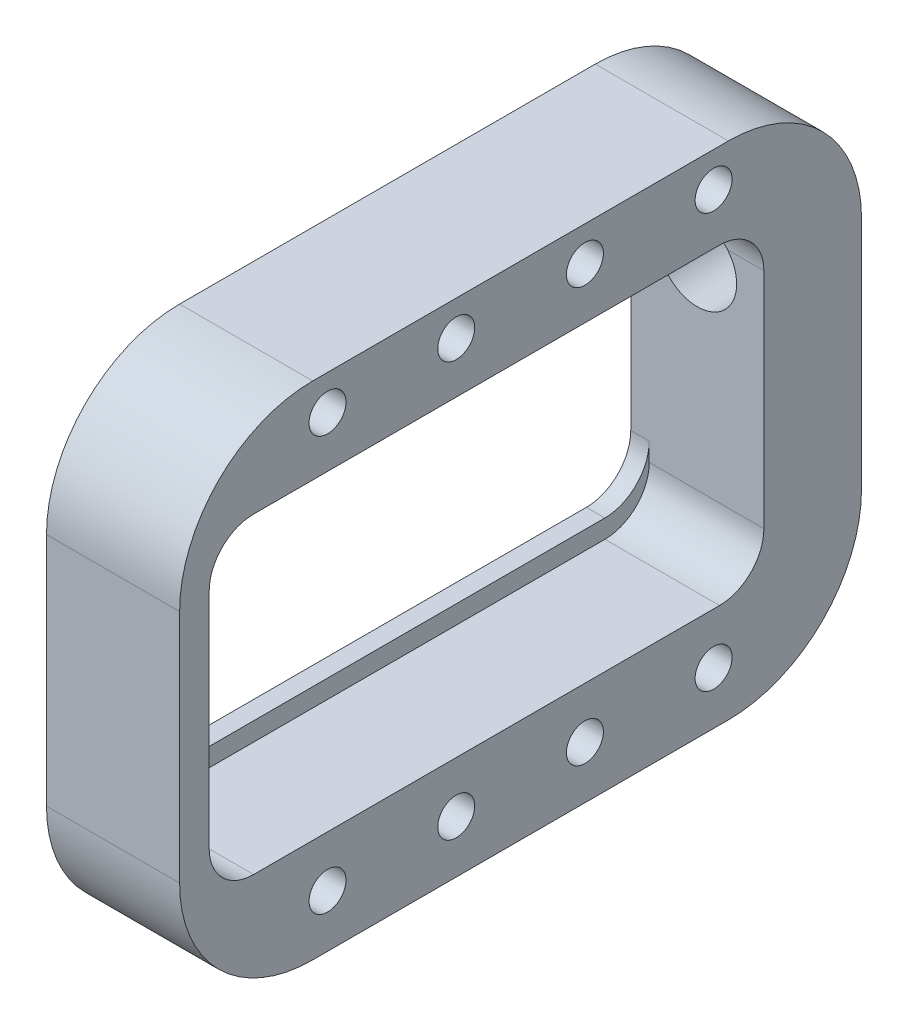
SolidWorks part; units mm, degrees
material "6061-T6 (SS)"
ref_plane "Front Plane" through (0, 0, 0) normal (0, 0, 1) x (1, 0, 0)
ref_plane "Top Plane" through (0, 0, 0) normal (0, 1, 0) x (1, 0, 0)
ref_plane "Right Plane" through (0, 0, 0) normal (1, 0, 0) x (0, 0, -1)
sketch "Sketch1" plane through (0, 0, 0) normal (1, 0, 0) x (0, 0, -1)
  line L0 (0, 22.2885) -> (0, -22.2885) construction
  line L1 (-26.3525, 22.2885) -> (32.1945, 22.2885)
  line L2 (-26.3525, 22.2885) -> (-26.3525, -22.2885)
  line L3 (-26.3525, -22.2885) -> (32.1945, -22.2885)
  line L4 (32.1945, 22.2885) -> (32.1945, -22.2885)
  line L5 (-23.8125, 13.3985) -> (23.8125, 13.3985)
  line L6 (-23.8125, 13.3985) -> (-23.8125, -13.3985)
  line L7 (-23.8125, -13.3985) -> (23.8125, -13.3985)
  line L8 (23.8125, 13.3985) -> (23.8125, -13.3985)
  line L9 (23.8125, -13.3985) -> (-23.8125, 13.3985) construction
  dimension "D1" = 8.89
  dimension "D2" = 2.54
  dimension "D3" = 47.625
  dimension "D4" = 26.797
  dimension "D5" = 8.382
  dimension "D6" = 8.89
extrude "Boss-Extrude1" add sketch "Sketch1" along normal mid plane 11.43
sketch "Sketch9" plane through (0, 0, -23.8125) normal (0, 0, 1) x (1, 0, 0)
  line L0 (-5.715, 13.3985) -> (-5.715, 11.811)
  line L1 (-5.715, -13.3985) -> (-4.1275, -13.3985)
  line L2 (-5.715, -13.3985) -> (-5.715, -11.811)
  line L3 (-5.715, -11.811) -> (-4.1275, -11.811)
  line L4 (-4.1275, -13.3985) -> (-4.1275, -11.811)
  line L5 (-5.715, 13.3985) -> (-4.1275, 13.3985)
  line L6 (-5.715, 11.811) -> (-4.1275, 11.811)
  line L7 (-4.1275, 13.3985) -> (-4.1275, 11.811)
  line L9 (-5.715, -13.3985) -> (-5.715, 13.3985) construction
  dimension "D1" = 23.622
  dimension "D2" = 1.5875
extrude "Boss-Extrude2" add sketch "Sketch9" along normal up to next
fillet "Fillet11" radius 3.81 4 edges at (-4.9213, -11.811, -23.8125) (-4.9212, 11.811, -23.8125) (-4.9213, -11.811, 23.8125) (-4.9212, 11.811, 23.8125)
fillet "Fillet12" radius 3.81 4 edges at (0.7937, 13.3985, 23.8125) (0.7937, -13.3985, 23.8125) (0.7938, -13.3985, -23.8125) (0.7937, 13.3985, -23.8125)
sketch "Sketch21" plane through (5.715, 0, 0) normal (1, 0, 0) x (0, 0, -1)
  line L0 (32.1945, -22.2885) -> (32.1945, 22.2885) construction
  line L1 (-26.3525, -22.2885) -> (32.1945, -22.2885) construction
  circle A0 centre (33.4645, -9.5885) radius 2.54
  dimension "D1" = 5.08
  dimension "D2" = 1.27
  dimension "D3" = 12.7
hole_wizard "1/4 Clearance Hole1" positions "Sketch5" profile "Sketch4" hole size "1/4" standard "ANSI Inch"
sketch "Sketch5" plane through (-2.5308, 6.493, -32.1945) normal (0, 0, 1) x (1, 0, 0)
  line L12 (8.2458, 15.7955) -> (8.2458, -28.7815) construction
  line L16 (-3.1842, -19.8915) -> (8.2458, -19.8915) construction
  line L17 (-3.1842, 15.7955) -> (-3.1842, -28.7815) construction
  line L26 (-3.1842, 6.9055) -> (8.2458, 6.9055) construction
  line L28 (2.5308, 6.9055) -> (2.5308, 0.9365) construction
  line L30 (2.5308, -19.8915) -> (2.5308, -13.9225) construction
  line L31 (2.5308, 0.9365) -> (2.5308, -13.9225) construction
  line L32 (8.2458, -28.7815) -> (8.2458, 15.7955) construction
  point P95 (2.5308, 0.9365)
  dimension "D1" = 5.969
sketch "Sketch4" plane through (0, 7.4295, -32.1945) normal (1, 0, 0) x (0, 1, 0)
  line L0 (0, 0) -> (0, 10.9198)
  line L1 (0, 10.9198) -> (3.3782, 8.89)
  line L2 (3.3782, 8.89) -> (3.3782, 0)
  line L5 (3.3782, 0) -> (0, 0)
  line L10 (0, 10.9198) -> (-3.3782, 8.89) construction
  line L11 (0, -6.35) -> (0, 107.95) construction
  dimension "Hole Dia." = 6.7564
  dimension "Hole Depth" = 8.89
  dimension "Drill Angle" = 118
sketch "Sketch14" plane through (-5.715, 0, 0) normal (-1, 0, 0) x (0, 0, 1)
  line L0 (-32.1945, -17.78) -> (-19.4945, -17.78) construction
  line L1 (-32.1945, 17.78) -> (-19.4945, 17.78) construction
  line L2 (-19.4945, 17.78) -> (-8.4455, 17.78) construction
  line L3 (13.6525, 17.78) -> (26.3525, 17.78) construction
  line L4 (-19.4945, -17.78) -> (-8.4455, -17.78) construction
  line L5 (13.6525, -17.78) -> (26.3525, -17.78) construction
  line L6 (-19.1091, 17.78) -> (-19.1091, 22.2885) construction
  line L7 (-7.0267, -17.78) -> (-7.0267, -22.2885) construction
  line L8 (-8.4455, -17.78) -> (2.6035, -17.78) construction
  line L9 (2.6035, -17.78) -> (13.6525, -17.78) construction
  line L10 (2.6035, 17.78) -> (13.6525, 17.78) construction
  line L11 (-8.4455, 17.78) -> (2.6035, 17.78) construction
  line L12 (26.3525, -22.2885) -> (-32.1945, -22.2885) construction
  line L13 (-32.1945, 22.2885) -> (26.3525, 22.2885) construction
  line L14 (26.3525, 22.2885) -> (26.3525, -22.2885) construction
  line L15 (-32.1945, -22.2885) -> (-32.1945, 22.2885) construction
  point P0 (-19.4945, 17.78)
  point P1 (-19.4945, -17.78)
  point P2 (13.6525, -17.78)
  point P3 (13.6525, 17.78)
  dimension "D1" = 12.7
  dimension "D2" = 35.56
hole_wizard "#6-32 Tapped Hole1" positions "Sketch16" profile "Sketch15" tap size "#6-32" standard "ANSI Inch" end condition through all
sketch "Sketch16" plane through (5.715, 17.9556, 19.2123) normal (-1, 0, 0) x (0, 0, 1)
  point P0 (-27.6578, -0.1756)
  point P3 (-16.6088, -0.1756)
  point P6 (-5.5598, -0.1756)
  point P9 (-38.7068, -0.1756)
  point P12 (-38.7068, -35.7356)
  point P15 (-27.6578, -35.7356)
  point P18 (-16.6088, -35.7356)
  point P21 (-5.5598, -35.7356)
cosmetic thread "Hole Thread1" parameters "D2"=3.5052
cosmetic thread "Hole Thread2" parameters "D2"=3.5052
cosmetic thread "Hole Thread3" parameters "D2"=3.5052
cosmetic thread "Hole Thread4" parameters "D2"=3.5052
cosmetic thread "Hole Thread5" parameters "D2"=3.5052
cosmetic thread "Hole Thread6" parameters "D2"=3.5052
cosmetic thread "Hole Thread7" parameters "D2"=3.5052
cosmetic thread "Hole Thread8" parameters "D2"=3.5052
sketch "Sketch15" plane through (5.715, 17.78, -8.4455) normal (0, 1, 0) x (0, 0, -1)
  line L0 (0, 0) -> (0, 11.43)
  line L1 (0, 11.43) -> (1.3525, 11.43)
  line L2 (1.3525, 11.43) -> (1.3525, 0)
  line L5 (1.3525, 0) -> (0, 0)
  line L11 (0, -6.35) -> (0, 107.95) construction
  dimension "Thru Tap Drill Dia." = 2.7051
  dimension "Thru Tap Drill Depth" = 11.43
sketch "Sketch22" plane through (-5.715, 0, 0) normal (-1, 0, 0) x (0, 0, 1)
  line L0 (-32.1945, 22.2885) -> (26.3525, 22.2885) construction
  line L1 (-32.1945, 29.9417) -> (26.3525, 29.9417)
  line L2 (-32.1945, 29.9417) -> (-32.1945, 20.7645)
  line L3 (-32.1945, 20.7645) -> (26.3525, 20.7645)
  line L4 (26.3525, 29.9417) -> (26.3525, 20.7645)
  line L5 (-32.1945, 29.9417) -> (26.3525, 20.7645) construction
  line L6 (-32.1945, 20.7645) -> (26.3525, 29.9417) construction
  line L7 (-32.1945, -22.2885) -> (-32.1945, 22.2885) construction
  line L8 (26.3525, 22.2885) -> (26.3525, -22.2885) construction
  point P4 (-2.921, 25.3531)
  dimension "D1" = 1.524
extrude "Cut-Extrude4" cut sketch "Sketch22" against normal through all
fillet "Fillet14" radius 11.43 2 edges at (0, -22.2885, 26.3525) (0, 20.7645, 26.3525)
fillet "Fillet13" radius 11.43 2 edges at (0, -22.2885, -32.1945) (0, 20.7645, -32.1945)
sketch "Sketch11" plane through (5.715, 0, 0) normal (1, 0, 0) x (0, 0, -1)
  line L0 (32.1945, -10.8585) -> (32.1945, 9.3345) construction
  line L1 (32.1945, 14.6923) -> (30.861, 14.6923)
  line L2 (32.1945, 14.6923) -> (32.1945, -16.2163)
  line L3 (32.1945, -16.2163) -> (30.861, -16.2163)
  line L4 (30.861, 14.6923) -> (30.861, -16.2163)
  arc A0 (20.7645, -22.2885) -> (32.1945, -10.8585) centre (20.7645, -10.8585) ccw construction
  arc A2 (32.1945, 9.3345) -> (20.7645, 20.7645) centre (20.7645, 9.3345) ccw construction
  dimension "D1" = 30.861
extrude "Cut-Extrude2" [suppressed] cut sketch "Sketch11" against normal blind 1.016
ref_point "Point1" [suppressed]
sketch "Sketch17" plane through (-5.715, 0, 0) normal (-1, 0, 0) x (0, 0, 1)
  line L0 (-44.2595, 37.338) -> (-44.2595, -38.862)
  line L1 (-44.2595, 37.338) -> (116.0145, 37.338)
  line L2 (-44.2595, -38.862) -> (116.0145, -38.862)
  line L3 (116.0145, 37.338) -> (116.0145, -38.862)
  line L4 (45.4025, 20.7645) -> (45.4025, -22.2885) construction
  line L5 (45.4025, 20.7645) -> (103.9495, 20.7645) construction
  line L6 (45.4025, -22.2885) -> (103.9495, -22.2885) construction
  line L7 (103.9495, 20.7645) -> (103.9495, -22.2885) construction
  line L8 (-32.1945, -0.762) -> (26.3525, -0.762) construction
  line L10 (26.3525, 9.3345) -> (26.3525, -10.8585) construction
  line L11 (-32.1945, -0.762) -> (-44.2595, -0.762) construction
  line L13 (14.9225, -22.2885) -> (-20.7645, -22.2885) construction
  line L14 (103.9495, -0.762) -> (116.0145, -0.762) construction
  line L15 (-44.2595, -38.862) -> (-40.3225, -42.799) construction
  line L16 (-40.3225, -42.799) -> (112.0775, -42.799) construction
  line L17 (112.0775, -42.799) -> (116.0145, -38.862) construction
  line L18 (-40.3225, -42.799) -> (-40.3225, -38.862) construction
  line L19 (112.0775, -42.799) -> (112.0775, -38.862) construction
  line L20 (26.3525, 9.3345) -> (26.3525, -10.8585) construction
  line L21 (-32.1945, -10.8585) -> (-32.1945, 9.3345) construction
  line L22 (-20.7645, 20.7645) -> (14.9225, 20.7645) construction
  dimension "D1" = 19.05
  dimension "D2" = 76.2
  dimension "D3" = 152.4
  dimension "D4" = 12.065
extrude "Maching Stock" [suppressed] add sketch "Sketch17" against normal blind 12.7 separate body
sketch "Sketch19" [suppressed] plane through (-5.715, 0, 0) normal (-1, 0, 0) x (0, 0, 1)
  line L0 (-8.001, 35.0972) -> (-8.001, -32.2156) construction
  line L1 (-8.001, -32.2156) -> (2.159, -32.2156) construction
  line L2 (2.159, -32.2156) -> (2.159, 32.3464) construction
  line L3 (34.7223, 4.318) -> (-40.8428, 4.318) construction
  line L4 (26.3525, -10.8585) -> (26.3525, 9.3345)
  line L5 (14.9225, 20.7645) -> (-20.7645, 20.7645)
  line L6 (-32.1945, 9.3345) -> (-32.1945, -10.8585)
  line L7 (-20.7645, -22.2885) -> (14.9225, -22.2885)
  line L8 (26.3525, -10.8585) -> (26.3525, -5.842)
  line L9 (14.9225, 20.7645) -> (-20.7645, 20.7645)
  line L10 (-32.1945, 9.3345) -> (-32.1945, 4.318)
  line L11 (-20.7645, -22.2885) -> (-8.001, -22.2885)
  line L12 (-40.8428, 4.318) -> (-40.8428, -5.842) construction
  line L13 (-40.8428, -5.842) -> (36.1785, -5.842) construction
  line L14 (2.159, -22.2885) -> (14.9225, -22.2885)
  line L15 (-8.001, 20.7645) -> (-20.7645, 20.7645)
  line L16 (26.3525, 4.318) -> (26.3525, 9.3345)
  line L17 (-32.1945, -5.842) -> (-32.1945, -10.8585)
  arc A4 (-20.7645, 20.7645) -> (-32.1945, 9.3345) centre (-20.7645, 9.3345) ccw
  arc A5 (-20.7645, 20.7645) -> (-32.1945, 9.3345) centre (-20.7645, 9.3345) ccw
  arc A6 (-32.1945, -10.8585) -> (-20.7645, -22.2885) centre (-20.7645, -10.8585) ccw
  arc A7 (14.9225, -22.2885) -> (26.3525, -10.8585) centre (14.9225, -10.8585) ccw
  arc A8 (26.3525, 9.3345) -> (14.9225, 20.7645) centre (14.9225, 9.3345) ccw
  arc A9 (26.3525, 9.3345) -> (14.9225, 20.7645) centre (14.9225, 9.3345) ccw
  arc A10 (-32.1945, -10.8585) -> (-20.7645, -22.2885) centre (-20.7645, -10.8585) ccw
  arc A11 (14.9225, -22.2885) -> (26.3525, -10.8585) centre (14.9225, -10.8585) ccw
  dimension "D2" = 10.16
  dimension "D1" = 0
sketch "Sketch20" plane through (5.715, 0, 0) normal (-1, 0, 0) x (0, 0, 1)
  line L0 (26.3525, 20.7645) -> (-125.3109, 20.7645) construction
  line L1 (26.3525, 9.3345) -> (26.3525, -10.8585) construction
  line L2 (-20.7645, 20.7645) -> (14.9225, 20.7645) construction
  dimension "D1" = 151.6634
ref_point "Point2"
ref_point "Point3"
sketch "Sketch23" plane through (-5.715, 0, 0) normal (-1, 0, 0) x (0, 0, 1)
  line L0 (0.6906, -22.2885) -> (26.3525, -22.2885) construction
  line L1 (14.9225, -22.2885) -> (-20.7645, -22.2885) construction
  line L2 (26.3525, 4.4099) -> (26.3525, -22.2885) construction
  line L3 (26.3525, 9.3345) -> (26.3525, -10.8585) construction
sketch "Sketch24" plane through (5.715, 0, 0) normal (1, 0, 0) x (0, 0, -1)
  circle A0 centre (19.4945, -17.78) radius 1.5875
  circle A1 centre (8.4455, -17.78) radius 1.5875
  circle A2 centre (-2.6035, -17.78) radius 1.5875
  circle A3 centre (-13.6525, -17.78) radius 1.5875
  circle A4 centre (-13.6525, 17.78) radius 1.5875
  circle A5 centre (-2.6035, 17.78) radius 1.5875
  circle A6 centre (8.4455, 17.78) radius 1.5875
  circle A7 centre (19.4945, 17.78) radius 1.5875
  dimension "D1" = 3.175
extrude "Cut-Extrude5" cut sketch "Sketch24" against normal up to surface (11.43 mm away) up to face at (-5.715, 17.78, -9.798)
